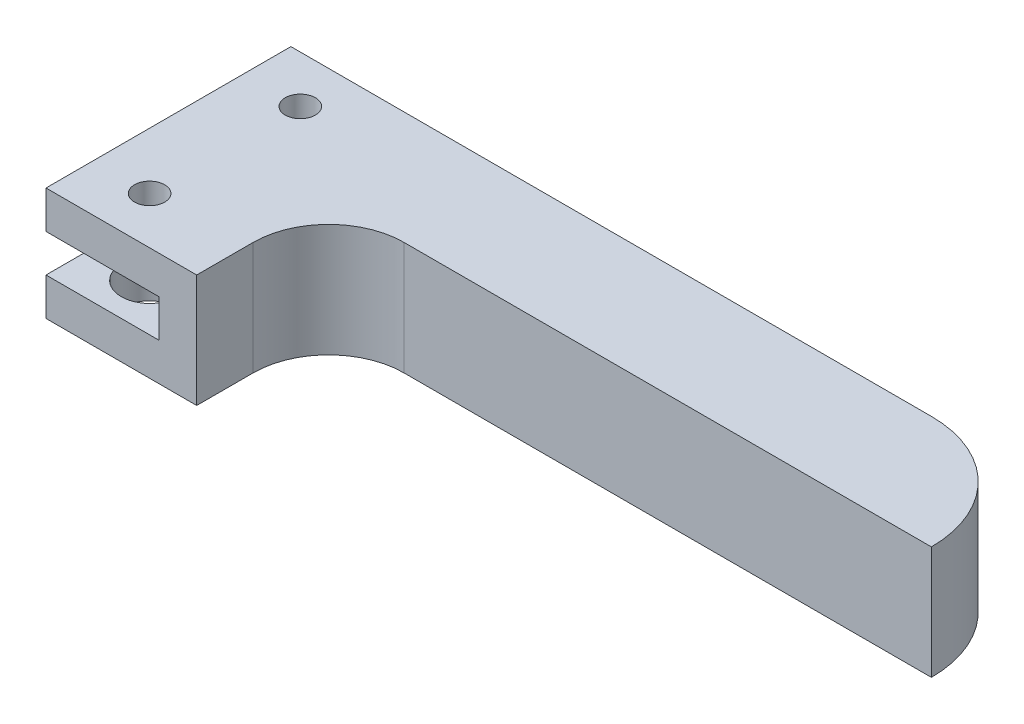
SolidWorks part; units mm, degrees
ref_plane "Front Plane" through (0, 0, 0) normal (0, 0, 1) x (1, 0, 0)
ref_plane "Top Plane" through (0, 0, 0) normal (0, 1, 0) x (1, 0, 0)
ref_plane "Right Plane" through (0, 0, 0) normal (1, 0, 0) x (0, 0, -1)
sketch "Sketch1" plane through (0, 0, 0) normal (0, 1, 0) x (1, 0, 0)
  line L1 (20, -6.5) -> (-20, -6.5)
  line L2 (20, -6.5) -> (20, 6.5)
  line L3 (20, 6.5) -> (-20, 6.5)
  line L4 (-20, -6.5) -> (-20, 6.5)
  line L5 (20, -6.5) -> (-20, 6.5) construction
  line L6 (20, 6.5) -> (-20, -6.5) construction
  point P0 (0, 0)
  dimension "D1" = 13
  dimension "D2" = 40
extrude "Boss-Extrude1" add sketch "Sketch1" along normal blind 6
sketch "Sketch2" plane through (0, 0, 6.5) normal (0, 0, 1) x (1, 0, 0)
  line L0 (-20, 6) -> (-20, 0) construction
  line L1 (-20, 4) -> (-14, 4)
  line L2 (-20, 4) -> (-20, 2)
  line L3 (-20, 2) -> (-14, 2)
  line L4 (-14, 4) -> (-14, 2)
  line L5 (-20, 0) -> (20, 0) construction
  point P6 (-20, 3)
  dimension "D1" = 2
  dimension "D2" = 6
  dimension "D3" = 3
extrude "Cut-Extrude1" cut sketch "Sketch2" against normal through all
sketch "Sketch3" plane through (0, 6, 0) normal (0, 1, 0) x (1, 0, 0)
  line L0 (-20, 6.5) -> (-20, -6.5) construction
  line L1 (20, 6.5) -> (-20, 6.5) construction
  circle A0 centre (-17, 4) radius 0.8
  circle A1 centre (-17, -4) radius 0.8
  dimension "D1" = 1.6
  dimension "D3" = 2.5
  dimension "D4" = 1.6
  dimension "D5" = 8
  dimension "D2" = 3
extrude "Cut-Extrude2" cut sketch "Sketch3" against normal blind 2
sketch "Sketch4" plane through (0, 6, 0) normal (0, 1, 0) x (1, 0, 0)
  line L1 (20, -6.5) -> (-12, -6.5)
  line L2 (20, -6.5) -> (20, 0.5)
  line L3 (20, 0.5) -> (-12, 0.5)
  line L4 (-12, -6.5) -> (-12, 0.5)
  dimension "D1" = 32
  dimension "D2" = 7
extrude "Cut-Extrude3" cut sketch "Sketch4" against normal through all
fillet "Fillet1" radius 4 1 edges at (-12, 3, -0.5)
fillet "Fillet3" radius 6 1 edges at (20, 3, -6.5)
sketch "Sketch5" plane through (0, 2, 0) normal (0, 1, 0) x (1, 0, 0)
  circle A0 centre (-17, 4) radius 1.5
  circle A1 centre (-17, -4) radius 1.5
  dimension "D1" = 3
  dimension "D2" = 3
extrude "Cut-Extrude4" cut sketch "Sketch5" against normal blind 2
